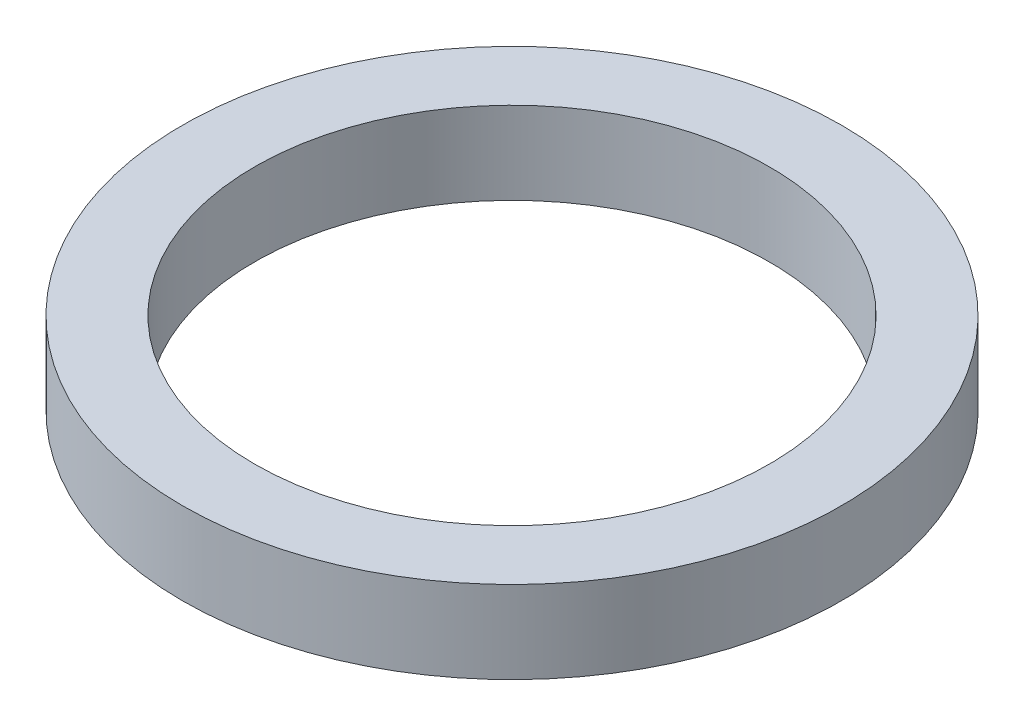
SolidWorks part; units mm, degrees
ref_plane "Front Plane" through (0, 0, 0) normal (0, 0, 1) x (1, 0, 0)
ref_plane "Top Plane" through (0, 0, 0) normal (0, 1, 0) x (1, 0, 0)
ref_plane "Right Plane" through (0, 0, 0) normal (1, 0, 0) x (0, 0, -1)
ref_plane "Plane1" through (0, 19, 0) normal (0, 1, 0) x (1, 0, 0)
sketch "Sketch1" plane through (0, 19, 0) normal (0, 1, 0) x (1, 0, 0)
  line L0 (0, 0) -> (-0.5, 0)
  circle A0 centre (-0.5, 0) radius 16
  circle A1 centre (-0.5, 0) radius 12.5
  dimension "D1" = 25
  dimension "D2" = 32
extrude "Boss-Extrude1" add sketch "Sketch1" along normal blind 4 contours A0 | A1
